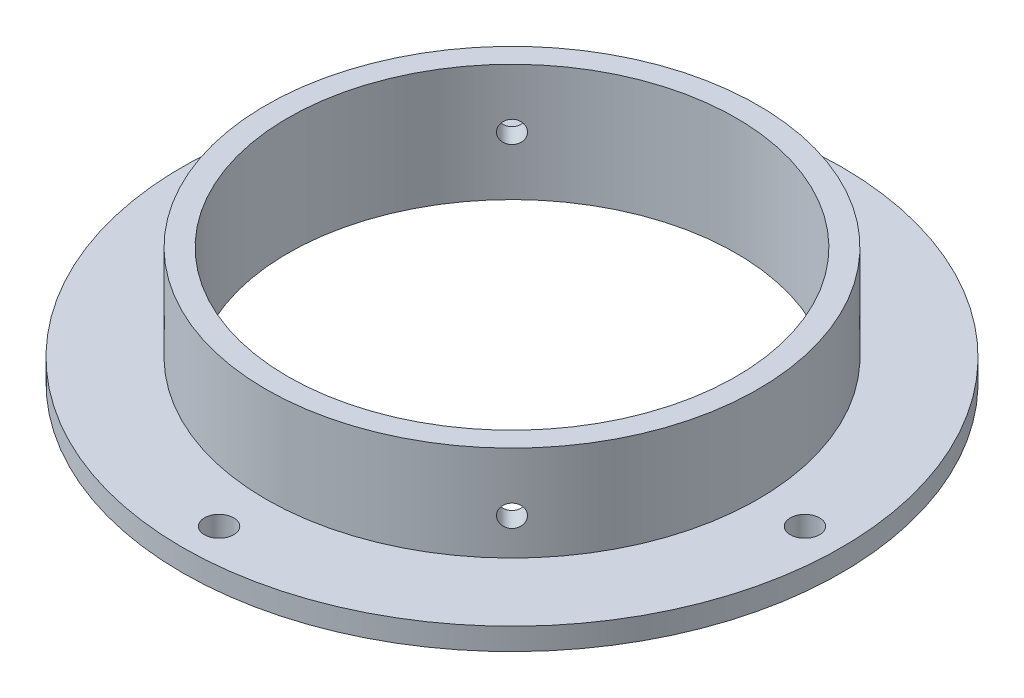
SolidWorks part; units mm, degrees
ref_plane "Front Plane" through (0, 0, 0) normal (0, 0, 1) x (1, 0, 0)
ref_plane "Top Plane" through (0, 0, 0) normal (0, 1, 0) x (1, 0, 0)
ref_plane "Right Plane" through (0, 0, 0) normal (1, 0, 0) x (0, 0, -1)
sketch "Sketch2" plane through (0, 0, 0) normal (0, 0, 1) x (1, 0, 0)
  line L0 (0, 31.8685) -> (0, -33.6468) construction
  line L1 (30.6, 16) -> (30.6, 0)
  line L2 (30.6, 0) -> (45, 0)
  line L3 (45, 0) -> (45, 3)
  line L4 (45, 3) -> (33.6, 3)
  line L5 (33.6, 3) -> (33.6, 16)
  line L6 (33.6, 16) -> (30.6, 16)
  dimension "D1" = 33.6
  dimension "D2" = 3
  dimension "D3" = 45
  dimension "D4" = 3
  dimension "D5" = 16
revolve "Revolve1" add sketch "Sketch2" angle 360 about L0
sketch "Sketch3" plane through (0, 3, 0) normal (0, 1, 0) x (1, 0, 0)
  line L0 (0, 69.3575) -> (0, -68.2374) construction
  line L1 (-78.2256, 0) -> (81.2127, 0) construction
  circle A0 centre (0, 40) radius 2
  circle A1 centre (40, 0) radius 2
  circle A2 centre (0, -40) radius 2
  circle A3 centre (-40, 0) radius 2
  circle A4 centre (0, 0) radius 40 construction
  point P9 (0, 0)
  point P16 (0, 0)
  dimension "D1" = 4
  dimension "D2" = 80
  dimension "D3" = 4
extrude "Cut-Extrude1" cut sketch "Sketch3" against normal through all
sketch "Sketch4" plane through (0, 0, 0) normal (0, 0, 1) x (1, 0, 0)
  line L0 (0, 0) -> (0, 58.4206) construction
ref_plane "Plane1" through (0, 0, 0) normal (0.7071, 0, 0.7071) x (0, 1, 0)
sketch "Sketch5" plane through (0, 0, 0) normal (0.7071, 0, 0.7071) x (0, 1, 0)
  line L0 (0, 0) -> (16, 0) construction
  line L1 (16, -33.6) -> (16, 33.6) construction
  circle A0 centre (8, 0) radius 1.5
  dimension "D1" = 3
extrude "Cut-Extrude2" cut sketch "Sketch5" against normal through all
pattern_circular "CirPattern1" count 4 over 360 about axis through (0, 31.8685, 0) along (0, 1, 0) of "Cut-Extrude2" reverse direction yes
